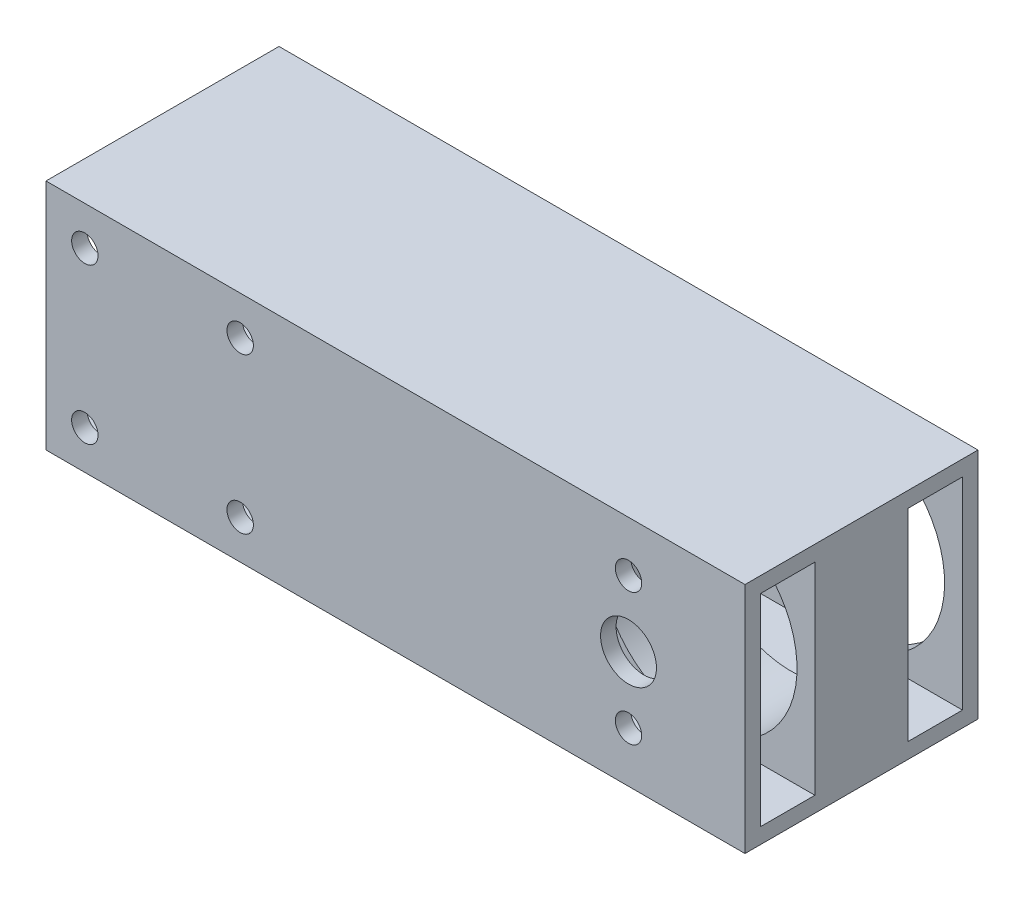
SolidWorks part; units mm, degrees
material "PLA 15%"
ref_plane "Front Plane" through (0, 0, 0) normal (0, 0, 1) x (1, 0, 0)
ref_plane "Top Plane" through (0, 0, 0) normal (0, 1, 0) x (1, 0, 0)
ref_plane "Right Plane" through (0, 0, 0) normal (1, 0, 0) x (0, 0, -1)
sketch "Sketch1" plane through (0, 0, 0) normal (1, 0, 0) x (0, 0, -1)
  line L1 (-15, -15) -> (15, -15)
  line L2 (-15, -15) -> (-15, 15)
  line L3 (-15, 15) -> (15, 15)
  line L4 (15, -15) -> (15, 15)
  line L5 (-15, -15) -> (15, 15) construction
  line L6 (-15, 15) -> (15, -15) construction
  line L11 (-5.1844, 5.1844) -> (5.1844, -5.1844) construction
  line L12 (-5.1844, -5.1844) -> (5.1844, 5.1844) construction
  line L13 (-13, 13) -> (-6, 13)
  line L14 (-13, 13) -> (-13, -13)
  line L15 (-13, -13) -> (-6, -13)
  line L16 (-6, 13) -> (-6, -13)
  line L17 (13, 13) -> (6, 13)
  line L18 (13, 13) -> (13, -13)
  line L19 (13, -13) -> (6, -13)
  line L20 (6, 13) -> (6, -13)
  point P0 (0, 0)
  point P7 (0, 0)
  dimension "D1" = 30
  dimension "D2" = 30
  dimension "D3" = 2
  dimension "D4" = 7
  dimension "D5" = 2
  dimension "D6" = 7
  dimension "D7" = 2
  dimension "D8" = 2
extrude "Boss-Extrude3" add sketch "Sketch1" along normal blind 90
sketch "Sketch6" plane through (0, 0, -15) normal (0, 0, -1) x (-1, 0, 0)
  line L0 (-90, -15) -> (-90, 15) construction
  circle A0 centre (-75, 0) radius 12.7
  dimension "D2" = 25.4
  dimension "D1" = 15
extrude "Cut-Extrude5" cut sketch "Sketch6" against normal blind 23
sketch "Sketch8" plane through (0, 0, 15) normal (0, 0, 1) x (1, 0, 0)
  line L0 (90, 15) -> (90, -15) construction
  line L1 (75, 0) -> (90, 0) construction
  circle A0 centre (75, 0) radius 3.6
  circle A1 centre (75, 8.5) radius 1.7
  circle A2 centre (75, -8.5) radius 1.7
  dimension "D2" = 7.2
  dimension "D5" = 3.4
  dimension "D1" = 15
  dimension "D3" = 17
extrude "Cut-Extrude6" cut sketch "Sketch8" against normal blind 17
sketch "Sketch9" plane through (0, 0, 0) normal (-1, 0, 0) x (0, 0, 1)
  line L0 (-6, 13) -> (6, 13)
  line L1 (-6, -13) -> (6, -13)
  line L2 (-6, 13) -> (-6, -13)
  line L3 (6, 13) -> (6, -13)
extrude "Cut-Extrude7" cut sketch "Sketch9" against normal blind 59
sketch "Sketch11" plane through (0, 0, 15) normal (0, 0, 1) x (1, 0, 0)
  line L13 (25, 10) -> (25, -10) construction
  line L16 (5, -10) -> (90, -10)
  line L17 (5, 10) -> (5, -10)
  line L18 (90, 10) -> (5, 10)
  line L19 (5, -10) -> (25, -10) construction
  line L20 (5, 10) -> (5, -10) construction
  line L21 (25, 10) -> (5, 10) construction
  point P12 (5, -10)
  point P14 (25, -10)
  point P15 (5, 10)
  point P16 (25, 10)
  dimension "D1" = 5
hole_wizard "M3 Clearance Hole1" positions "Sketch11" profile "Sketch12" hole size "M3" standard "ANSI Metric" end condition through all
sketch "Sketch12" plane through (25, 10, 15) normal (1, 0, 0) x (0, -1, 0)
  line L0 (0, 0) -> (0, 30)
  line L1 (0, 30) -> (1.7, 30)
  line L2 (1.7, 30) -> (1.7, 0)
  line L5 (1.7, 0) -> (0, 0)
  line L11 (0, -6.35) -> (0, 107.95) construction
  dimension "Thru Hole Dia." = 3.4
  dimension "Thru Hole Depth" = 30
sketch "Sketch13" [suppressed] plane through (0, 0, 0) normal (0, 0, 1) x (1, 0, 0)
  line L0 (0, -5.3647) -> (20.3647, 15)
  line L1 (0, 15) -> (0, -15) construction
  line L2 (90, 15) -> (0, 15) construction
  line L3 (20.3647, 15) -> (0, 15)
  line L4 (0, 15) -> (0, -5.3647)
  dimension "D1" = 45
  dimension "D2" = 28.8
extrude "Cut-Extrude8" [suppressed] cut sketch "Sketch13" against normal blind 26 and the other way blind 28
